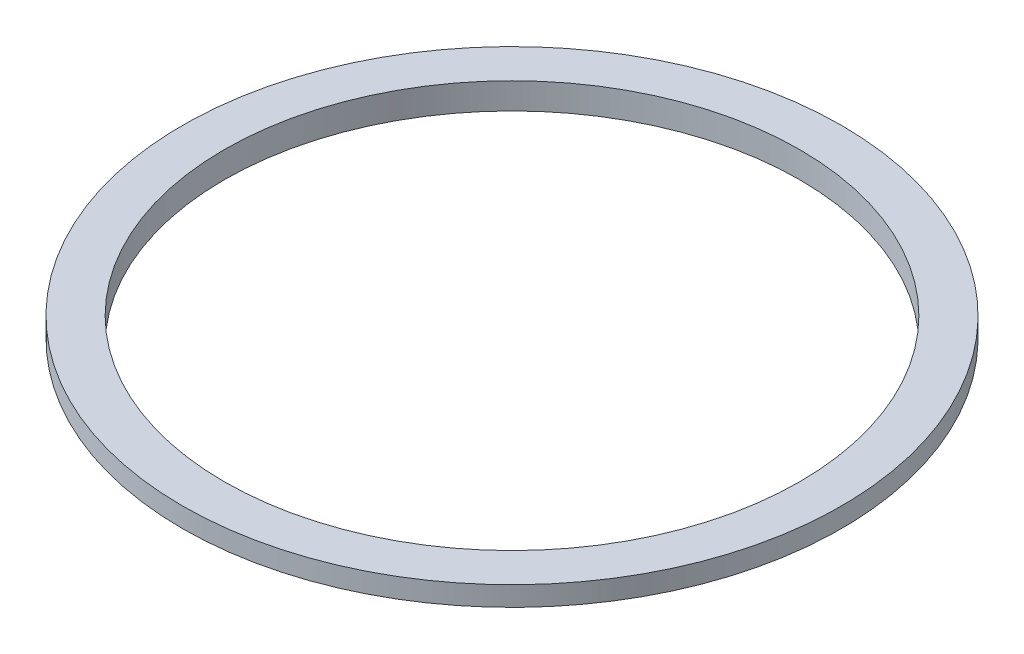
SolidWorks part; units mm, degrees
material "Stainless Steel (ferritic)"
ref_plane "Front Plane" through (0, 0, 0) normal (0, 0, 1) x (1, 0, 0)
ref_plane "Top Plane" through (0, 0, 0) normal (0, 1, 0) x (1, 0, 0)
ref_plane "Right Plane" through (0, 0, 0) normal (1, 0, 0) x (0, 0, -1)
sketch "Sketch1" plane through (0, 0, 0) normal (0, 0, 1) x (1, 0, 0)
  line L0 (0, -28.6657) -> (0, 30.2732) construction
  line L1 (0, 0) -> (73.9023, 0) construction
  line L2 (29.375, -1.4963) -> (27.8787, 0)
  line L3 (27.5, -2.5) -> (32.5, -2.5)
  line L4 (27.5, -2.5) -> (27.5, 2.5)
  line L5 (27.5, 2.5) -> (32.5, 2.5)
  line L6 (32.5, -2.5) -> (32.5, 2.5)
  line L7 (27.5, -2.5) -> (32.5, 2.5) construction
  line L8 (27.5, 2.5) -> (32.5, -2.5) construction
  line L9 (30.625, -1.4963) -> (32.1213, 0)
  line L10 (27.8787, 0) -> (29.375, 1.4963)
  line L11 (32.1213, 0) -> (30.625, 1.4963)
  line L12 (30, -2.1213) -> (30, 2.1213) construction
  line L13 (27.8787, 0) -> (32.1213, 0) construction
  line L14 (29.375, 1.4963) -> (29.375, 2.1213)
  line L15 (29.375, 2.1213) -> (30.625, 2.1213)
  line L16 (30.625, 2.1213) -> (30.625, 1.4963)
  line L17 (29.375, -1.4963) -> (29.375, -2.1213)
  line L18 (29.375, -2.1213) -> (30.625, -2.1213)
  line L19 (30.625, -2.1213) -> (30.625, -1.4963)
  circle A0 centre (30, 0) radius 1.5 construction
  point P5 (30, 0)
  dimension "D3" = 3
  dimension "D1" = 27.5
  dimension "D2" = 5
  dimension "D4" = 5
  dimension "D5" = 1.25
  dimension "D6" = 0.625
  dimension "D7" = 0.625
  dimension "D8" = 0.625
  dimension "D9" = 0.625
  dimension "D10" = 0.625
  dimension "D11" = 1.25
revolve "Revolve1" add sketch "Sketch1" angle 360 about L0
sketch "Sketch2" plane through (0, 0, 0) normal (0, 0, 1) x (1, 0, 0)
  line L0 (0, 0) -> (0, 27.7757) construction
  line L1 (0, 0) -> (88.8981, 0) construction
  line L2 (-32.5, -2.5) -> (32.5, -2.5) construction
  line L3 (27.5, 0) -> (31.5, 0)
  line L4 (27.5, 0) -> (27.5, -2.5)
  line L5 (27.5, -2.5) -> (32.5, -2.5)
  line L6 (32.5, 0) -> (32.5, -2.5)
  line L9 (31.5, 0) -> (31.5, 2.5)
  line L10 (31.5, 2.5) -> (32.5, 2.5)
  line L11 (32.5, 0) -> (32.5, 2.5)
  dimension "D1" = 27.5
  dimension "D2" = 5
  dimension "D3" = 2.5
  dimension "D4" = 2.5
  dimension "D5" = 1
revolve "Cut-Revolve1" cut sketch "Sketch2" angle 360 about L0
ref_axis "Axis1" through (0, 2.625, 0) along (0, -1, 0)
